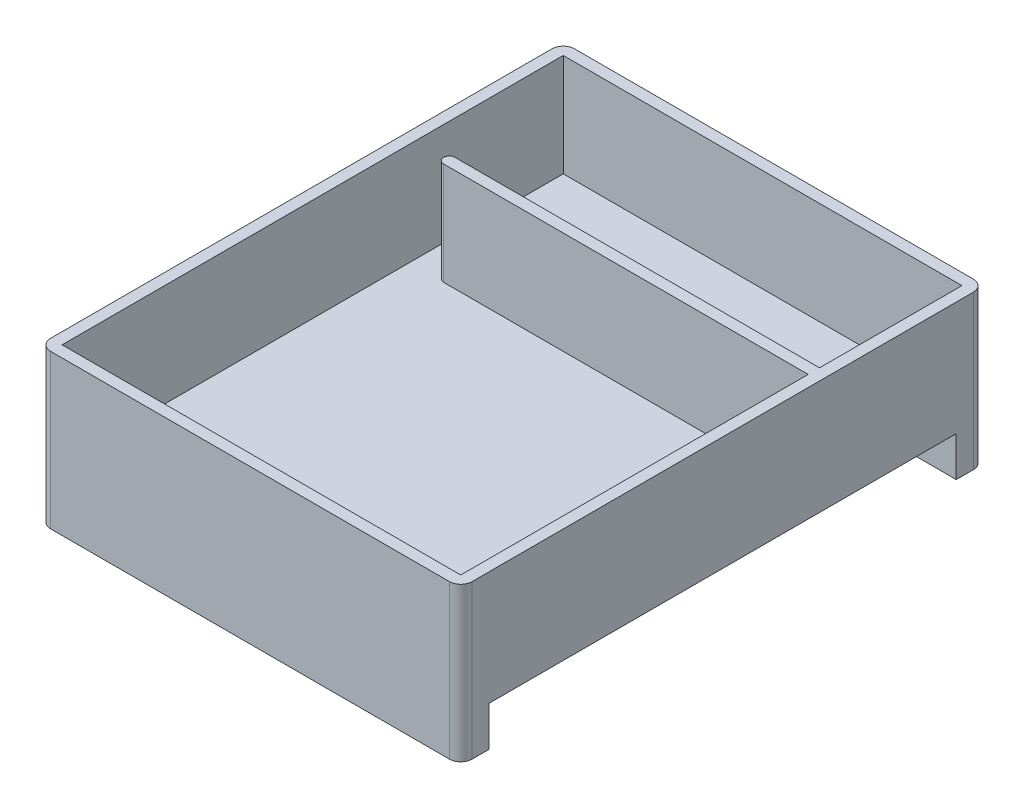
SolidWorks part; units mm, degrees
ref_plane "前视基准面" through (0, 0, 0) normal (0, 0, 1) x (1, 0, 0)
ref_plane "上视基准面" through (0, 0, 0) normal (0, 1, 0) x (1, 0, 0)
ref_plane "右视基准面" through (0, 0, 0) normal (1, 0, 0) x (0, 0, -1)
other "Configuration Table"
sketch "草图1" plane through (0, 0, 0) normal (0, 1, 0) x (1, 0, 0)
  line L1 (0, 0) -> (74, 0)
  line L2 (0, 0) -> (0, 65)
  line L3 (0, 65) -> (74, 65)
  line L4 (74, 0) -> (74, 65)
  dimension "D1" = 74
  dimension "D2" = 65
extrude "凸台-拉伸1" add sketch "草图1" along normal blind 20
sketch "草图2" plane through (0, 20, 0) normal (0, 1, 0) x (1, 0, 0)
  line L4 (2, 63) -> (72, 63)
  line L5 (2, 63) -> (2, 2)
  line L6 (2, 2) -> (72, 2)
  line L7 (72, 63) -> (72, 2)
  dimension "D1" = 70
  dimension "D2" = 61
extrude "切除-拉伸1" cut sketch "草图2" against normal blind 18
sketch "草图3" plane through (0, 20, 0) normal (0, 1, 0) x (1, 0, 0)
  line L0 (2, 63) -> (2, 65)
  line L1 (74, 65) -> (0, 65) construction
  line L2 (2, 65) -> (7, 65)
  line L3 (7, 65) -> (7, 63)
  line L4 (72, 63) -> (2, 63) construction
  line L5 (7, 63) -> (2, 63)
  dimension "D1" = 5
extrude "切除-拉伸2" cut sketch "草图3" against normal blind 18
sketch "草图4" plane through (0, 0, 0) normal (0, -1, 0) x (1, 0, 0)
  line L1 (0, -65) -> (74, -65)
  line L2 (0, -65) -> (0, -92)
  line L3 (0, -92) -> (74, -92)
  line L4 (74, -65) -> (74, -92)
  dimension "D1" = 27
extrude "凸台-拉伸2" add sketch "草图4" against normal blind 20
sketch "草图5" plane through (0, 20, 0) normal (0, 1, 0) x (1, 0, 0)
  line L0 (7, 65) -> (74, 65)
  line L1 (74, 0) -> (74, 92) construction
  line L2 (2, 65) -> (2, 90)
  line L6 (2, 90) -> (72, 90)
  line L8 (72, 90) -> (72, 65)
  line L9 (7, 65) -> (2, 65)
  line M8 (2, 65) -> (7, 65)
extrude "切除-拉伸3" cut sketch "草图5" against normal blind 18 contours L8 L6 L2 L0 M8 region at (37, 20, -77.5)
sketch "草图6" plane through (0, 0, 0) normal (0, -1, 0) x (1, 0, 0)
  line L0 (74, 0) -> (74, -92) construction
  line L1 (0, 0) -> (74, 0)
  line L2 (0, 0) -> (0, -5)
  line L3 (0, -5) -> (74, -5)
  line L4 (74, 0) -> (74, -5)
  line L6 (0, -92) -> (74, -92)
  line L7 (0, -92) -> (0, -87)
  line L8 (0, -87) -> (74, -87)
  line L9 (74, -92) -> (74, -87)
  dimension "D1" = 5
  dimension "D2" = 5
extrude "凸台-拉伸3" add sketch "草图6" along normal blind 7
fillet "圆角1" radius 2 1 edges at (0, 6.5, 0)
fillet "圆角2" radius 2 1 edges at (74, 6.5, 0)
fillet "圆角3" radius 2 2 edges at (0, 6.5, -92) (74, 6.5, -92)
fillet "圆角5" radius 1 2 edges at (7, 11, -65) (7, 11, -63)
